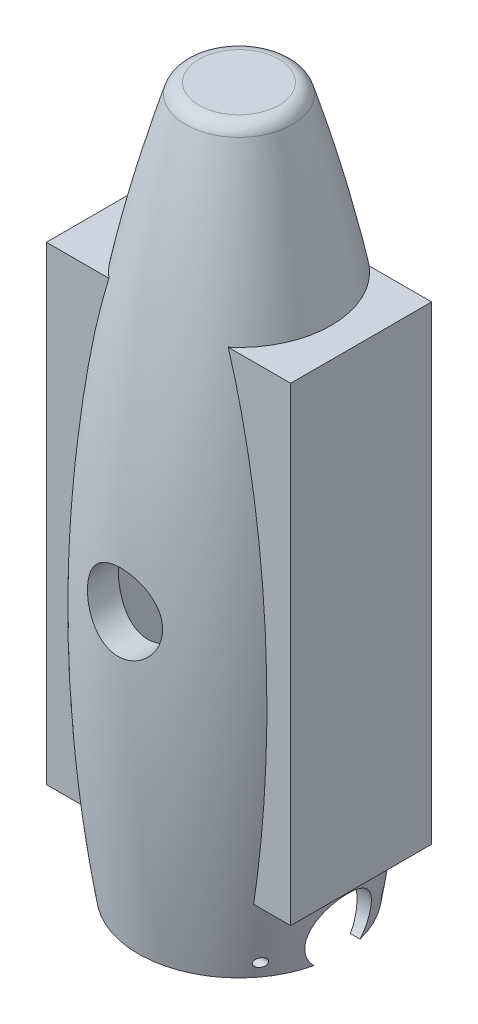
SolidWorks part; units mm, degrees
ref_plane "Front Plane" through (0, 0, 0) normal (0, 0, 1) x (1, 0, 0)
ref_plane "Top Plane" through (0, 0, 0) normal (0, 1, 0) x (1, 0, 0)
ref_plane "Right Plane" through (0, 0, 0) normal (1, 0, 0) x (0, 0, -1)
sketch "Sketch2" plane through (0, 0, 0) normal (0, 0, 1) x (1, 0, 0)
  line L0 (0, 145) -> (0, -5) construction
  line L1 (0, 145) -> (0, -5)
  line L2 (21.4243, -5) -> (0, -5)
  line L3 (0, 145) -> (21.4243, 145) construction
  line L5 (0, 145) -> (10.7121, 145)
  spline S1 degree 2 poles (10.7121, 145) (33.8436, 71.2518) (21.4243, -5) knots 0 0 0 1 1 1
  point P0 (21.4243, -5)
  point P2 (0, 145)
  point P9 (21.4243, 145)
  point P12 (10.7121, 145)
  point P14 (0, 70)
  point P16 (25, 70)
  dimension "D1" = 22
  dimension "D2" = 150
  dimension "D3" = 5
  dimension "D4" = 25
ref_axis "Central Axis" through (0, 157.5, 0) along (0, -1, 0)
revolve "Main Body" add sketch "Sketch2" angle 360 about L1
fillet "Fillet on Top Edge" radius 3 1 edges at (0, 145, 10.7121)
sketch "Sketch4" plane through (0, 145, 0) normal (0, 1, 0) x (1, 0, 0)
  circle A0 centre (0, 0) radius 8
  dimension "D1" = 16
extrude "Cut for Top Button" [suppressed] cut sketch "Sketch4" against normal up to next
sketch "Sketch7" plane through (0, 0, 0) normal (1, 0, 0) x (0, 0, -1)
  circle A0 centre (0, 0) radius 7
  dimension "D1" = 14
extrude "Cut for Wires" cut sketch "Sketch7" along normal through all
sketch "Sketch8" plane through (0, -5, 0) normal (0, -1, 0) x (1, 0, 0)
  circle A0 centre (0, 0) radius 19.4243
  circle A1 centre (0, 0) radius 21.4243 construction
  dimension "D1" = 2
extrude "Cut for Hollow Inside" cut sketch "Sketch8" against normal blind 105
sketch "Sketch9" plane through (0, 0, 0) normal (0, 0, 1) x (1, 0, 0)
  line L0 (0, 157.5) -> (0, -7.5) construction
  circle A0 centre (0, 60) radius 8
  dimension "D1" = 16
  dimension "D2" = 60
extrude "Cut for Side Button" cut sketch "Sketch9" along normal through all
ref_plane "Left Side" through (26, 0, 0) normal (1, 0, 0) x (0, 0, -1)
ref_plane "Right Side" through (-26, 0, 0) normal (1, 0, 0) x (0, 0, -1)
sketch "Sketch10" plane through (-26, 0, 0) normal (1, 0, 0) x (0, 0, -1)
  line L0 (-19.4243, -5) -> (19.4243, -5) construction
  line L1 (-15, 10) -> (15, 10)
  line L2 (-15, 10) -> (-15, 110)
  line L3 (-15, 110) -> (15, 110)
  line L4 (15, 10) -> (15, 110)
  line L5 (-15, 10) -> (15, 110) construction
  line L6 (-15, 110) -> (15, 10) construction
  point P0 (0, 60)
  point P5 (0, -5)
  dimension "D1" = 65
  dimension "D2" = 100
  dimension "D3" = 30
extrude "Right PCB Plate" add sketch "Sketch10" along normal up to next
mirror "Left PCB Plate" about plane through (0, 0, 0) normal (1, 0, 0) of "Right PCB Plate"
sketch "Sketch11" plane through (0, 0, 0) normal (1, 0, 0) x (0, 0, -1)
  line L0 (0, 157.5) -> (0, -7.5) construction
  circle A0 centre (-13, -2) radius 1
  circle A1 centre (13, -2) radius 1
  point P0 (13, 0)
  point P1 (13, -2)
  point P4 (-13, -2)
  dimension "D4" = 2
  dimension "D5" = 2
  dimension "D1" = 13
  dimension "D2" = 2
  dimension "D3" = 13
extrude "Cuts for Body Screw Holes" cut sketch "Sketch11" against normal through all both and the other way through all
sketch "Sketch12" plane through (0, 100, 0) normal (0, -1, 0) x (1, 0, 0)
  circle A0 centre (0, 0) radius 9
  dimension "D1" = 18
extrude "Another Cut for Hollow Inside" cut sketch "Sketch12" against normal blind 40
